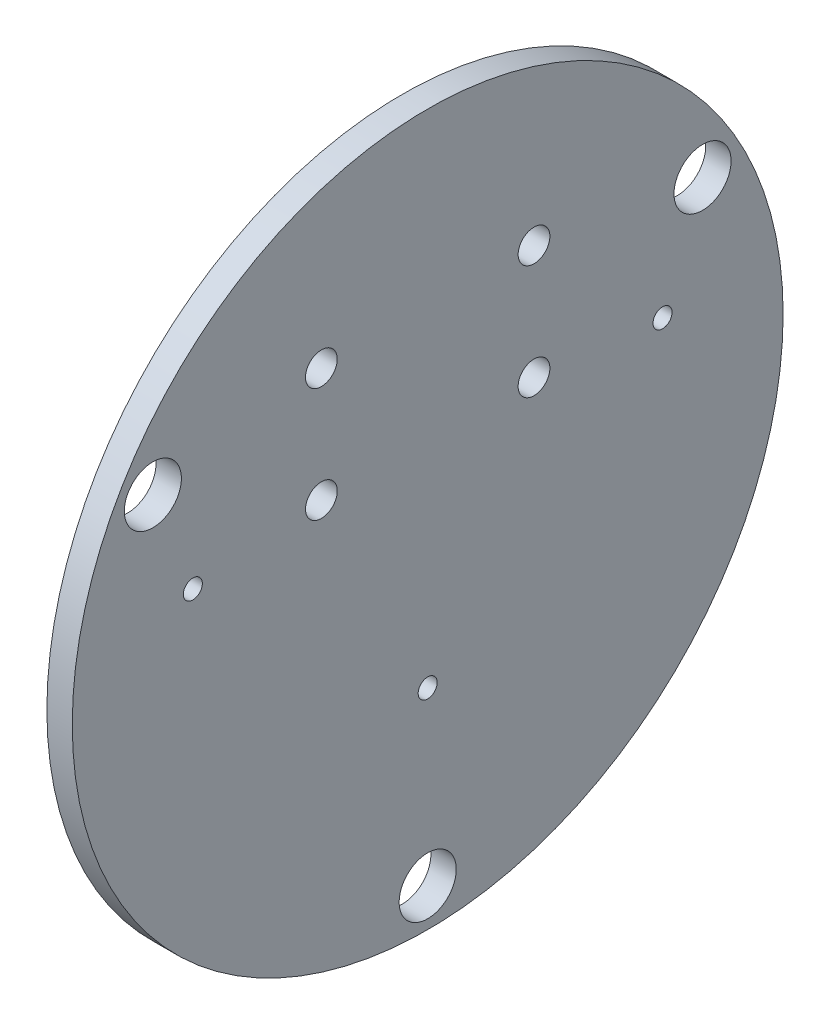
SolidWorks part; units mm, degrees
ref_plane "Ebene vorne" through (0, 0, 0) normal (0, 0, 1) x (1, 0, 0)
ref_plane "Ebene oben" through (0, 0, 0) normal (0, 1, 0) x (1, 0, 0)
ref_plane "Ebene rechts" through (0, 0, 0) normal (1, 0, 0) x (0, 0, -1)
sketch "Sketch1" plane through (0, 0, 0) normal (1, 0, 0) x (0, 0, -1)
  circle A0 centre (0, 0) radius 56
  dimension "D1" = 112
extrude "Boss-Extrude1" add sketch "Sketch1" along normal blind 4
sketch "Sketch2" plane through (0, 0, 0) normal (-1, 0, 0) x (0, 0, 1)
  line L0 (0, 0) -> (0, -56) construction
  circle A0 centre (-43.3013, 25) radius 4.5
  circle A1 centre (43.3013, 25) radius 4.5
  circle A2 centre (0, -50) radius 4.5
  circle A3 centre (0, 0) radius 56 construction
  point P4 (19.9187, -77.6338)
  point P9 (0, 0)
  point P12 (0, -56)
  point P15 (0, 0)
  point P16 (0, 0)
  point P17 (0, 0)
  point P18 (0, 0)
  point P19 (0, 0)
  dimension "D1" = 9
  dimension "D2" = 50
  dimension "D3" = 3
extrude "Cut-Extrude1" cut sketch "Sketch2" against normal through all
sketch "Sketch4" plane through (4, 0, 0) normal (1, 0, 0) x (0, 0, -1)
  line L0 (0, 56) -> (0, -40.0081) construction
  line L1 (16.75, 28.9955) -> (-48.2229, 28.9955) construction
  circle A0 centre (-16.75, 28.9955) radius 2.5
  circle A1 centre (16.75, 28.9955) radius 2.5
  circle A2 centre (16.75, 11) radius 2.5
  circle A3 centre (-16.75, 11) radius 2.5
  circle A4 centre (-37, 9) radius 1.5
  circle A5 centre (0, -23) radius 1.5
  circle A6 centre (37, 9) radius 1.5
  circle A7 centre (0, 0) radius 56 construction
  circle A8 centre (0, -50) radius 4.5 construction
  dimension "D1" = 5
  dimension "D2" = 3
  dimension "D5" = 33.5
  dimension "D7" = 2
  dimension "D3" = 32
  dimension "D4" = 17.9955
  dimension "D6" = 32
  dimension "D8" = 27
extrude "Cut-Extrude3" cut sketch "Sketch4" against normal through all
